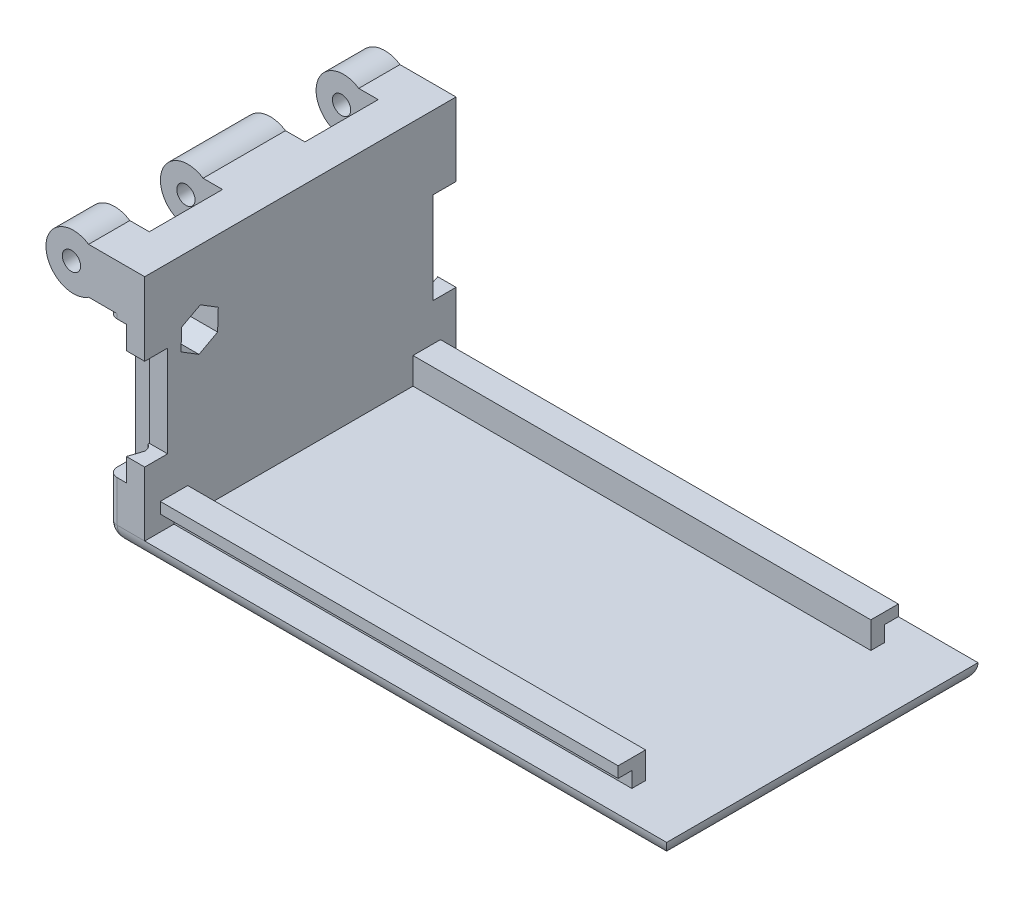
SolidWorks part; units mm, degrees
ref_plane "Front Plane" through (0, 0, 0) normal (0, 0, 1) x (1, 0, 0)
ref_plane "Top Plane" through (0, 0, 0) normal (0, 1, 0) x (1, 0, 0)
ref_plane "Right Plane" through (0, 0, 0) normal (1, 0, 0) x (0, 0, -1)
sketch "Sketch1" plane through (0, 0, 0) normal (0, 1, 0) x (1, 0, 0)
  line L1 (0, 0) -> (61, 0)
  line L2 (0, 0) -> (0, 34)
  line L3 (0, 34) -> (61, 34)
  line L4 (61, 0) -> (61, 34)
  line L5 (0, 0) -> (61, 34) construction
  line L6 (0, 34) -> (61, 0) construction
  point P4 (30.5, 17)
  dimension "D1" = 34
  dimension "D2" = 61
extrude "Boss-Extrude1" add sketch "Sketch1" along normal blind 2
sketch "Sketch2" plane through (0, 2, 0) normal (0, 1, 0) x (1, 0, 0)
  line L0 (61, 34) -> (0, 34) construction
  line L1 (0, 0) -> (4, 0)
  line L2 (0, 0) -> (0, 34)
  line L3 (0, 34) -> (4, 34)
  line L4 (4, 0) -> (4, 34)
  line L5 (0, 0) -> (4, 34) construction
  line L6 (0, 34) -> (4, 0) construction
  point P4 (2, 17)
  dimension "D1" = 4
extrude "Boss-Extrude2" add sketch "Sketch2" along normal blind 25 contours L4 L3 L2 L1
sketch "Sketch3" plane through (4, 0, 0) normal (1, 0, 0) x (0, 0, -1)
  line L0 (0, 2) -> (34, 2) construction
  line L1 (4.7, 2) -> (3.2, 2)
  line L2 (4.7, 2) -> (4.7, 4.9)
  line L3 (4.7, 4.9) -> (3.2, 4.9)
  line L4 (3.2, 2) -> (3.2, 4.9)
  line L5 (4.7, 2) -> (3.2, 4.9) construction
  line L6 (4.7, 4.9) -> (3.2, 2) construction
  line L7 (0, 27) -> (0, 2) construction
  line L8 (3.2, 4.9) -> (1.7, 4.9)
  line L9 (3.2, 4.9) -> (3.2, 3.7)
  line L10 (3.2, 3.7) -> (1.7, 3.7)
  line L11 (1.7, 4.9) -> (1.7, 3.7)
  line L12 (3.2, 4.9) -> (1.7, 3.7) construction
  line L13 (3.2, 3.7) -> (1.7, 4.9) construction
  line L14 (17, 2) -> (17, 9.9529) construction
  line L15 (30.8, 3.7) -> (32.3, 3.7)
  line L16 (32.3, 4.9) -> (32.3, 3.7)
  line L17 (30.8, 4.9) -> (32.3, 4.9)
  line L18 (30.8, 4.9) -> (30.8, 3.7)
  line L19 (29.3, 4.9) -> (30.8, 4.9)
  line L20 (30.8, 2) -> (30.8, 4.9)
  line L21 (29.3, 2) -> (30.8, 2)
  line L22 (29.3, 2) -> (29.3, 4.9)
  point P4 (3.95, 3.45)
  point P10 (2.45, 4.3)
  dimension "D1" = 1.2
  dimension "D2" = 2.9
  dimension "D3" = 1.5
  dimension "D4" = 3.2
  dimension "D5" = 1.5
extrude "Boss-Extrude3" add sketch "Sketch3" along normal blind 50 contours L17 L18 L15 L16 | L4 L1 L2 L3 | L8 L11 L10 L9 | L20 L21 L22 L19 region at (4, 4.3, -31.55)
sketch "Sketch4" plane through (0, 0, 0) normal (0, 0, 1) x (1, 0, 0)
  line L0 (0, 27) -> (0, 0) construction
  line L1 (4, 27) -> (0, 27)
  line L2 (4, 27) -> (4, 22)
  line L3 (4, 22) -> (0, 22)
  line L5 (4, 27) -> (-5, 22) construction
  line L6 (4, 22) -> (-3.9994, 26.8988) construction
  line L8 (0, 22) -> (-2.1254, 22)
  line L9 (0, 27) -> (-2.1254, 27)
  line L10 (0, 22) -> (0, 27)
  circle A1 centre (-3.7837, 24.5) radius 3
  point P4 (-0.281, 24.6217)
  line M12 (0, 27) -> (0, 0)
  dimension "D3" = 6
  dimension "D1" = 8
  dimension "D2" = 5
extrude "Boss-Extrude4" add sketch "Sketch4" against normal blind 34 contours M12 | A1 region at (-0.6518, 24.5, 0)
sketch "Sketch5" plane through (0, 0, 0) normal (0, -1, 0) x (1, 0, 0)
  line L0 (0, -34) -> (0, 0) construction
  line L1 (0, -4.5) -> (-8, -4.5)
  line L2 (0, -4.5) -> (0, -12.5)
  line L3 (0, -12.5) -> (-8, -12.5)
  line L4 (-8, -4.5) -> (-8, -12.5)
  line L5 (0, -4.5) -> (-8, -12.5) construction
  line L6 (0, -12.5) -> (-8, -4.5) construction
  line L7 (61, -34) -> (0, -34) construction
  line L8 (0, -21.5) -> (-8, -21.5)
  line L9 (0, -21.5) -> (0, -29.5)
  line L10 (0, -29.5) -> (-8, -29.5)
  line L11 (-8, -21.5) -> (-8, -29.5)
  line L12 (0, -21.5) -> (-8, -29.5) construction
  line L13 (0, -29.5) -> (-8, -21.5) construction
  line L14 (0, 0) -> (61, 0) construction
  point P4 (-4, -8.5)
  point P11 (-4, -25.5)
  dimension "D1" = 8
  dimension "D2" = 8
  dimension "D3" = 4.5
  dimension "D4" = 4.5
  dimension "D5" = 8
  dimension "D6" = 8
extrude "Cut-Extrude1" cut sketch "Sketch5" against normal blind 30 contours L3 L4 L1 L2 | L8 L11 L10 L9
sketch "Sketch6" plane through (0, 0, 0) normal (0, 0, 1) x (1, 0, 0)
  line L1 (0, 22) -> (0, 0) construction
  circle A0 centre (-4, 24.5) radius 1
  dimension "D1" = 2
  dimension "D2" = 4
extrude "Cut-Extrude2" cut sketch "Sketch6" against normal blind 33
sketch "Sketch7" plane through (0, 0, 0) normal (-1, 0, 0) x (0, 0, 1)
  line L0 (0, 22) -> (0, 0) construction
  line L1 (-8.0352, 20.0914) -> (-7.9628, 17.7832)
  line L2 (-7.9628, 17.7832) -> (-5.9276, 16.6917)
  line L3 (-5.9276, 16.6917) -> (-3.9648, 17.9086)
  line L4 (-3.9648, 17.9086) -> (-4.0372, 20.2168)
  line L5 (-4.0372, 20.2168) -> (-6.0724, 21.3083)
  line L6 (-6.0724, 21.3083) -> (-8.0352, 20.0914)
  line L7 (-4.5, 27) -> (-12.5, 27) construction
  circle A0 centre (-6, 19) radius 2 construction
  dimension "D1" = 4
  dimension "D2" = 6
  dimension "D3" = 8
extrude "Cut-Extrude3" cut sketch "Sketch7" against normal blind 28
fillet "Fillet1" radius 2 4 edges at (30.5, 0, 0) (61, 0, -17) (30.5, 0, -34) (0, 0, -17)
fillet "Fillet3" radius 1 4 edges at (0.5858, 0.5858, -33.4142) (0.5858, 0.5858, -0.5858) (0, 12, -34) (0, 12, 0)
sketch "Sketch8" plane through (0, 0, -34) normal (0, 0, -1) x (-1, 0, 0)
  line L0 (2.1254, 27) -> (-4, 27) construction
  line L1 (0, 6.5) -> (-2, 6.5)
  line L2 (0, 6.5) -> (0, 21.5)
  line L3 (0, 21.5) -> (-2, 21.5)
  line L4 (-2, 6.5) -> (-2, 21.5)
  line L5 (0, 6.5) -> (-2, 21.5) construction
  line L6 (0, 21.5) -> (-2, 6.5) construction
  line L7 (-4, 27) -> (-4, 2) construction
  point P4 (-1, 14)
  dimension "D1" = 5.5
  dimension "D2" = 15
  dimension "D3" = 2
  dimension "D4" = 2
extrude "Cut-Extrude4" cut sketch "Sketch8" against normal blind 3 contours L2 L3 L4 L1
sketch "Sketch9" plane through (2, 0, 0) normal (-1, 0, 0) x (0, 0, 1)
  line L0 (-34, 6.5) -> (-34, 21.5) construction
  line L1 (-34, 9) -> (-31.5, 9)
  line L2 (-34, 9) -> (-34, 19)
  line L3 (-34, 19) -> (-31.5, 19)
  line L4 (-31.5, 9) -> (-31.5, 19)
  line L5 (-34, 9) -> (-31.5, 19) construction
  line L6 (-34, 19) -> (-31.5, 9) construction
  line L7 (-31, 21.5) -> (-34, 21.5) construction
  point P4 (-32.75, 14)
  dimension "D1" = 10
  dimension "D2" = 2.5
  dimension "D3" = 2.5
extrude "Cut-Extrude5" cut sketch "Sketch9" against normal blind 3 contours L1 L4 L3 L2
sketch "Sketch11" plane through (0, 0, 0) normal (0, 0, 1) x (1, 0, 0)
  line L0 (-2.1254, 27) -> (4, 27) construction
  line L1 (2, 21.5) -> (0, 21.5)
  line L2 (2, 21.5) -> (2, 6.5)
  line L3 (2, 6.5) -> (0, 6.5)
  line L4 (0, 21.5) -> (0, 6.5)
  line L5 (2, 21.5) -> (0, 6.5) construction
  line L6 (2, 6.5) -> (0, 21.5) construction
  line L7 (4, 27) -> (4, 2) construction
  point P4 (1, 14)
  dimension "D1" = 15
  dimension "D2" = 5.5
  dimension "D3" = 2
extrude "Cut-Extrude6" cut sketch "Sketch11" against normal blind 3
sketch "Sketch12" plane through (2, 0, 0) normal (-1, 0, 0) x (0, 0, 1)
  line L0 (0, 6.5) -> (0, 21.5) construction
  line L1 (0, 9) -> (-2.5, 9)
  line L2 (0, 9) -> (0, 19)
  line L3 (0, 19) -> (-2.5, 19)
  line L4 (-2.5, 9) -> (-2.5, 19)
  line L5 (0, 9) -> (-2.5, 19) construction
  line L6 (0, 19) -> (-2.5, 9) construction
  line L7 (0, 6.5) -> (-1, 6.5) construction
  point P4 (-1.25, 14)
  dimension "D1" = 10
  dimension "D2" = 2.5
  dimension "D3" = 2.5
extrude "Cut-Extrude7" cut sketch "Sketch12" against normal blind 3
sketch "Sketch13" plane through (0, 0, 0) normal (0, -1, 0) x (-1, 0, 0)
  line L0 (-59, 22) -> (-2, 22) construction
  line L1 (-59, 32) -> (-59, 2) construction
  line L2 (-2, 2) -> (-2, 32) construction
  line L3 (-59, 2) -> (-2, 2) construction
  text T0 "FORCE" font "Century Gothic" height in points 45
  dimension "D1" = 20
extrude "Cut-Extrude8" cut sketch "Sketch13" against normal blind 1.2
sketch "Sketch14" plane through (0, 6.5, 0) normal (0, 1, 0) x (1, 0, 0)
  line L0 (1, 34) -> (2, 34) construction
  line L1 (2, 31) -> (2, 34) construction
  line L2 (2, 34) -> (2.5, 32.5)
  line L4 (2, 33.366) -> (2, 34)
  arc A0 (2, 33.366) -> (2.5, 32.5) centre (1.5, 32.5) ccw
  dimension "D1" = 2
  dimension "D2" = 1.5
  dimension "D3" = 0.5
extrude "Cut-Extrude10" cut sketch "Sketch14" along normal blind 15 contours A0 L2 L4
sketch "Sketch15" plane through (0, 21.5, 0) normal (0, -1, 0) x (1, 0, 0)
  line L0 (2, -3) -> (2, 0) construction
  line L1 (2, 0) -> (1, 0) construction
  line L2 (2, 0) -> (2.5, -1.5)
  line L4 (2, 0) -> (2, -0.634)
  arc A0 (2, -0.634) -> (2.5, -1.5) centre (1.5, -1.5) ccw
  dimension "D1" = 2
  dimension "D2" = 0.5
  dimension "D3" = 1.5
extrude "Cut-Extrude11" cut sketch "Sketch15" along normal blind 15
